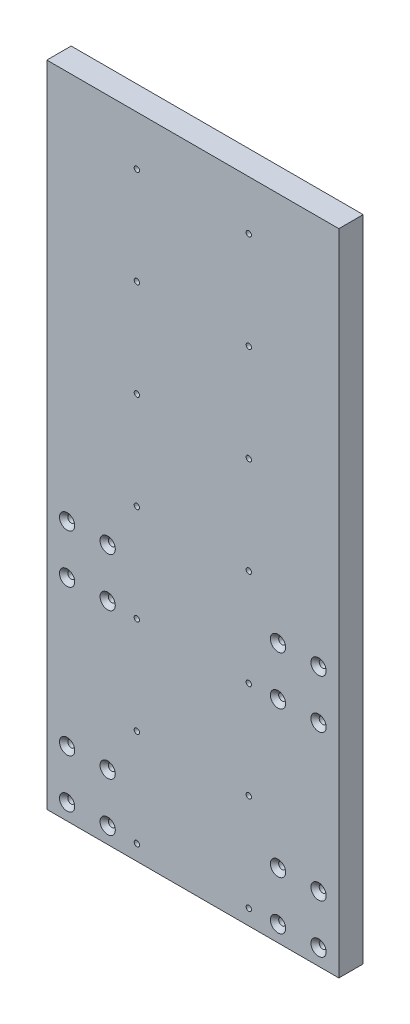
SolidWorks part; units mm, degrees
ref_plane "Front Plane" through (0, 0, 0) normal (0, 0, 1) x (1, 0, 0)
ref_plane "Top Plane" through (0, 0, 0) normal (0, 1, 0) x (1, 0, 0)
ref_plane "Right Plane" through (0, 0, 0) normal (1, 0, 0) x (0, 0, -1)
sketch "Sketch1" plane through (0, 0, 0) normal (0, 0, 1) x (1, 0, 0)
  line L1 (90, 200) -> (-90, 200)
  line L2 (90, 200) -> (90, -200)
  line L3 (90, -200) -> (-90, -200)
  line L4 (-90, 200) -> (-90, -200)
  line L5 (90, 200) -> (-90, -200) construction
  line L6 (90, -200) -> (-90, 200) construction
  point P0 (0, 0)
  dimension "D1" = 180
  dimension "D2" = 400
extrude "Boss-Extrude1" add sketch "Sketch1" along normal blind 15 contours L1 L4 L3 L2
sketch "Sketch3" plane through (0, 0, 15) normal (0, 0, 1) x (1, 0, 0)
  line L0 (-77.5, -190) -> (-77.5, -200)
  line L1 (90, -200) -> (-90, -200) construction
  line L2 (-90, 200) -> (-90, -200) construction
  point P0 (-77.5, -160)
  point P3 (-52.5, -160)
  point P4 (-52.5, -190)
  point P5 (-77.5, -190)
  point P7 (52.5, -160)
  point P8 (77.5, -160)
  point P9 (77.5, -190)
  point P10 (52.5, -190)
  point P11 (52.5, -40)
  point P12 (77.5, -40)
  point P13 (77.5, -70)
  point P14 (52.5, -70)
  point P15 (-77.5, -40)
  point P16 (-52.5, -40)
  point P17 (-52.5, -70)
  point P18 (-77.5, -70)
  dimension "D5" = 10
  dimension "D6" = 12.5
  dimension "D1" = 2
  dimension "D2" = 2
  dimension "D3" = 2
  dimension "D4" = 2
hole_wizard "CSK for M4 Flat Head Machine Screw1" positions "Sketch3" profile "Sketch4" countersink size "M4" standard "ANSI Metric" end condition through all
sketch "Sketch4" plane through (-77.5, -160, 15) normal (1, 0, 0) x (0, -1, 0)
  line L0 (0, 0) -> (0, 15)
  line L1 (0, 15) -> (2.15, 15)
  line L2 (2.15, 15) -> (2.15, 2.55)
  line L3 (2.15, 2.55) -> (4.7, 0)
  line L5 (4.7, 0) -> (0, 0)
  line L6 (-2.15, 2.55) -> (-4.7, 0) construction
  line L11 (0, -6.35) -> (0, 107.95) construction
  dimension "Thru Hole Dia." = 4.3
  dimension "Thru Hole Depth" = 15
  dimension "Near C'Sink Dia." = 9.4
  dimension "Near C'Sink Angle" = 90
sketch "Sketch5" plane through (0, 0, 15) normal (0, 0, 1) x (1, 0, 0)
  line L0 (90, -200) -> (-90, -200) construction
  circle A0 centre (52.5, -190) radius 2.15 construction
  circle A1 centre (-52.5, -190) radius 4.7 construction
  point P0 (-34.5, -190.5)
  point P1 (34.5, -190.5)
  point P8 (-34.5, -130.5)
  point P10 (34.5, -130.5)
  point P11 (-34.5, -70.5)
  point P12 (34.5, -70.5)
  point P13 (-34.5, -10.5)
  point P14 (34.5, -10.5)
  point P15 (-34.5, 49.5)
  point P16 (34.5, 49.5)
  point P17 (-34.5, 109.5)
  point P18 (34.5, 109.5)
  point P19 (-34.5, 169.5)
  point P20 (34.5, 169.5)
  dimension "D1" = 9.5
  dimension "D2" = 9.5
  dimension "D3" = 18
  dimension "D4" = 18
  dimension "D5" = 7
hole_wizard "M4x0.7 Tapped Hole1" positions "Sketch5" profile "Sketch6" tap size "M4x0.7" standard "ANSI Metric" end condition through all
sketch "Sketch6" plane through (-34.5, -190.5, 15) normal (1, 0, 0) x (0, -1, 0)
  line L0 (0, 0) -> (0, 15)
  line L1 (0, 15) -> (1.65, 15)
  line L2 (1.65, 15) -> (1.65, 0)
  line L5 (1.65, 0) -> (0, 0)
  line L11 (0, -6.35) -> (0, 107.95) construction
  dimension "Thru Tap Drill Dia." = 3.3
  dimension "Thru Tap Drill Depth" = 15
cosmetic thread "Hole Thread1"
cosmetic thread "Hole Thread2"
cosmetic thread "Hole Thread3"
cosmetic thread "Hole Thread4"
cosmetic thread "Hole Thread5"
cosmetic thread "Hole Thread6"
cosmetic thread "Hole Thread7"
cosmetic thread "Hole Thread8"
cosmetic thread "Hole Thread9"
cosmetic thread "Hole Thread10"
cosmetic thread "Hole Thread11"
cosmetic thread "Hole Thread12"
cosmetic thread "Hole Thread13"
cosmetic thread "Hole Thread14"
